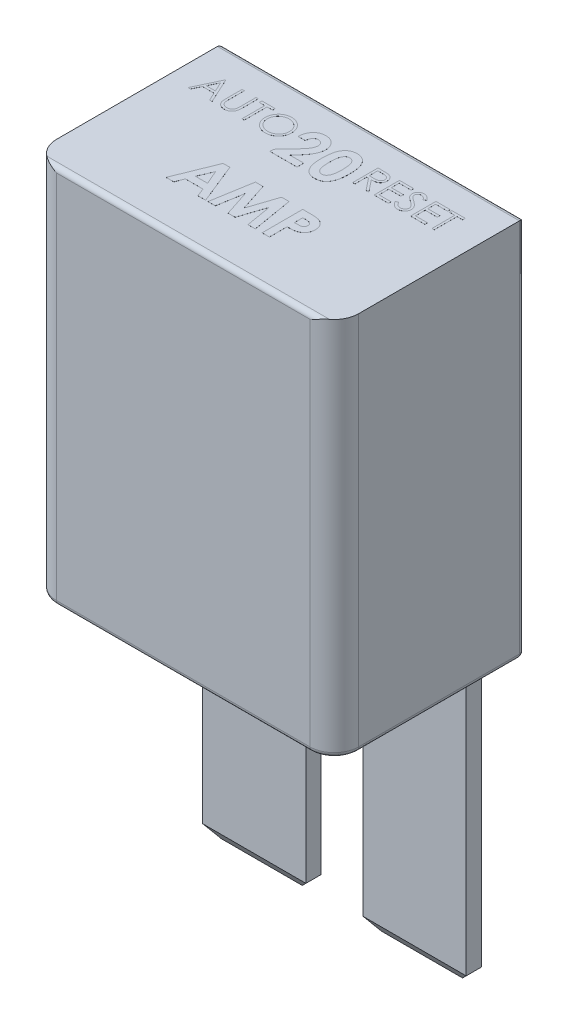
SolidWorks part; units mm, degrees
material "Free-Cutting Brass, UNS C36000"
ref_plane "Front Plane" through (0, 0, 0) normal (0, 0, 1) x (1, 0, 0)
ref_plane "Top Plane" through (0, 0, 0) normal (0, 1, 0) x (1, 0, 0)
ref_plane "Right Plane" through (0, 0, 0) normal (1, 0, 0) x (0, 0, -1)
sketch "Sketch1" plane through (0, 0, 0) normal (0, 1, 0) x (1, 0, 0)
  line L5 (-7.874, -4.953) -> (7.874, -4.953)
  line L6 (-7.874, -4.953) -> (-7.874, 4.953)
  line L7 (-7.874, 4.953) -> (7.874, 4.953)
  line L8 (7.874, -4.953) -> (7.874, 4.953)
  line L9 (-7.874, -4.953) -> (7.874, 4.953) construction
  line L10 (-7.874, 4.953) -> (7.874, -4.953) construction
  point P4 (0, 0)
  dimension "D3" = 9.906
  dimension "D4" = 15.748
extrude "Extrude1" add sketch "Sketch1" along normal blind 19.812
fillet "Fillet1" radius 1.27 2 edges at (7.874, 9.906, 4.953) (-7.874, 9.906, 4.953)
fillet "Fillet2" radius 0.254 10 edges at (7.874, 9.906, -4.953) (0, 19.812, -4.953) (-7.874, 9.906, -4.953) (0, 0, -4.953) (-7.874, 0, -0.635) (-7.502, 0, 4.581) (0, 0, 4.953) (7.502, 0, 4.581) (7.874, 0, -0.635) (0, 19.812, 4.953) tangent propagation no
sketch "Sketch2" plane through (0, 0, 0) normal (0, -1, 0) x (1, 0, 0)
  line L0 (-1.4859, -2.9261) -> (-6.8707, -2.9261)
  line L1 (-6.8707, -2.9261) -> (-6.8707, -3.7135)
  line L2 (-6.8707, -3.7135) -> (-1.4859, -3.7135)
  line L3 (-1.4859, -3.7135) -> (-1.4859, -2.9261)
  line L4 (7.62, -4.953) -> (-7.62, -4.953) construction
  line L5 (-7.874, -4.699) -> (-7.874, 3.683) construction
  dimension "D1" = 5.3848
  dimension "D2" = 0.7874
  dimension "D3" = 1.2395
  dimension "D4" = 1.0033
extrude "Extrude2" add sketch "Sketch2" along normal blind 14.478
chamfer "Chamfer1" distance 0.5842 angle 45 2 edges at (-6.8707, -14.478, -3.3198) (-1.4859, -14.478, -3.3198)
chamfer "Chamfer2" distance 0.5842 angle 34 2 edges at (-4.1783, -14.478, -3.7135) (-4.1783, -14.478, -2.9261) first distance on face at (-4.1783, -9.4573, -3.7135) first distance on face at (-4.1783, -9.4573, -2.9261)
mirror "Mirror1" about plane through (0, 0, 0) normal (1, 0, 0) of "Chamfer2", "Chamfer1", "Extrude2"
sketch "Sketch3" plane through (0, 19.812, 0) normal (0, 1, 0) x (1, 0, 0)
  line L0 (-7.874, 4.699) -> (-7.874, -3.683) construction
  line L1 (7.874, 4.699) -> (-7.874, 4.699) construction
  text T0 "AUTO       RESET\r\n\r\n" font "Century Gothic" height in points 5
  text T1 "<b>20</b>\r\n" font "Century Gothic" height in points 8
  text T2 "<b>AMP</b>" font "Century Gothic" height in points 8
  dimension "D1" = 1.0253
  dimension "D2" = 4.5342
  dimension "D3" = 6.0571
  dimension "D4" = 2.6239
  dimension "D5" = 3.3711
  dimension "D6" = 7.2501
extrude "Extrude3" add sketch "Sketch3" along normal blind 0.0025
